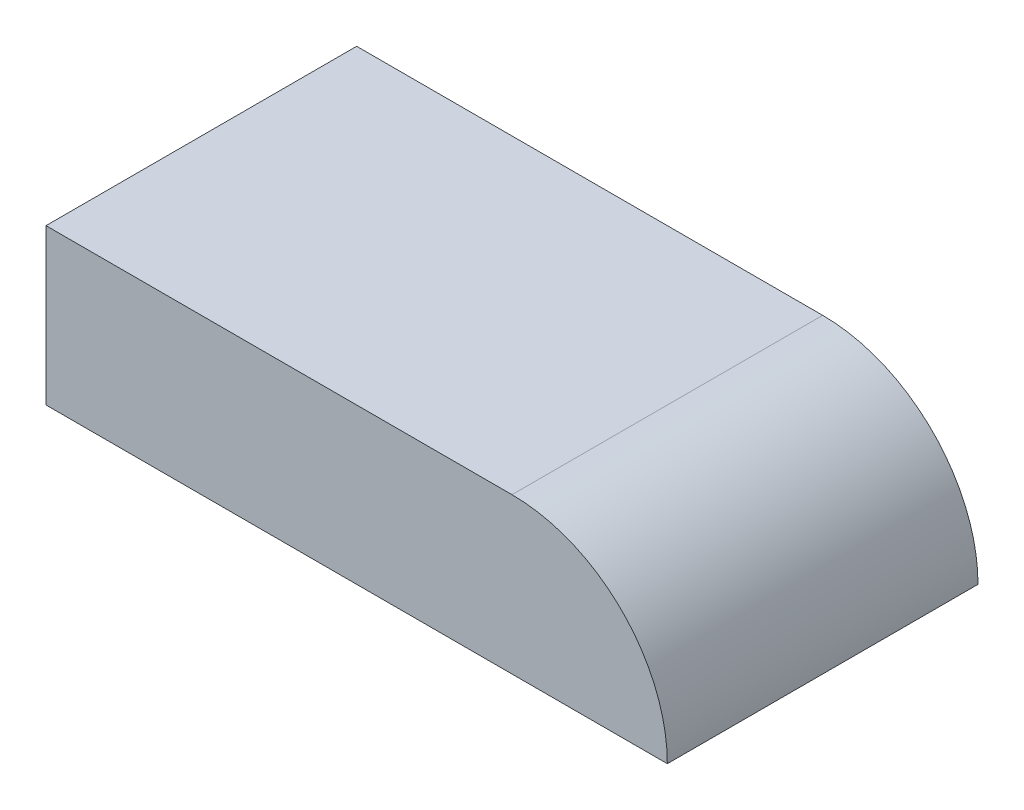
SolidWorks part; units mm, degrees
ref_plane "Front" through (0, 0, 0) normal (0, 0, 1) x (1, 0, 0)
ref_plane "Top" through (0, 0, 0) normal (0, 1, 0) x (1, 0, 0)
ref_plane "Right" through (0, 0, 0) normal (1, 0, 0) x (0, 0, -1)
sketch "Esquisse1" plane through (0, 0, 0) normal (0, 0, 1) x (1, 0, 0)
  line L1 (0, 0) -> (20, 0)
  line L2 (0, 0) -> (0, 5)
  line L3 (0, 5) -> (20, 5)
  line L4 (20, 0) -> (20, 5)
  dimension "D1" = 5
  dimension "D2" = 20
extrude "Boss.-Extru.1" add sketch "Esquisse1" along normal blind 10
fillet "Congé1" radius 5 1 edges at (20, 5, 5)
